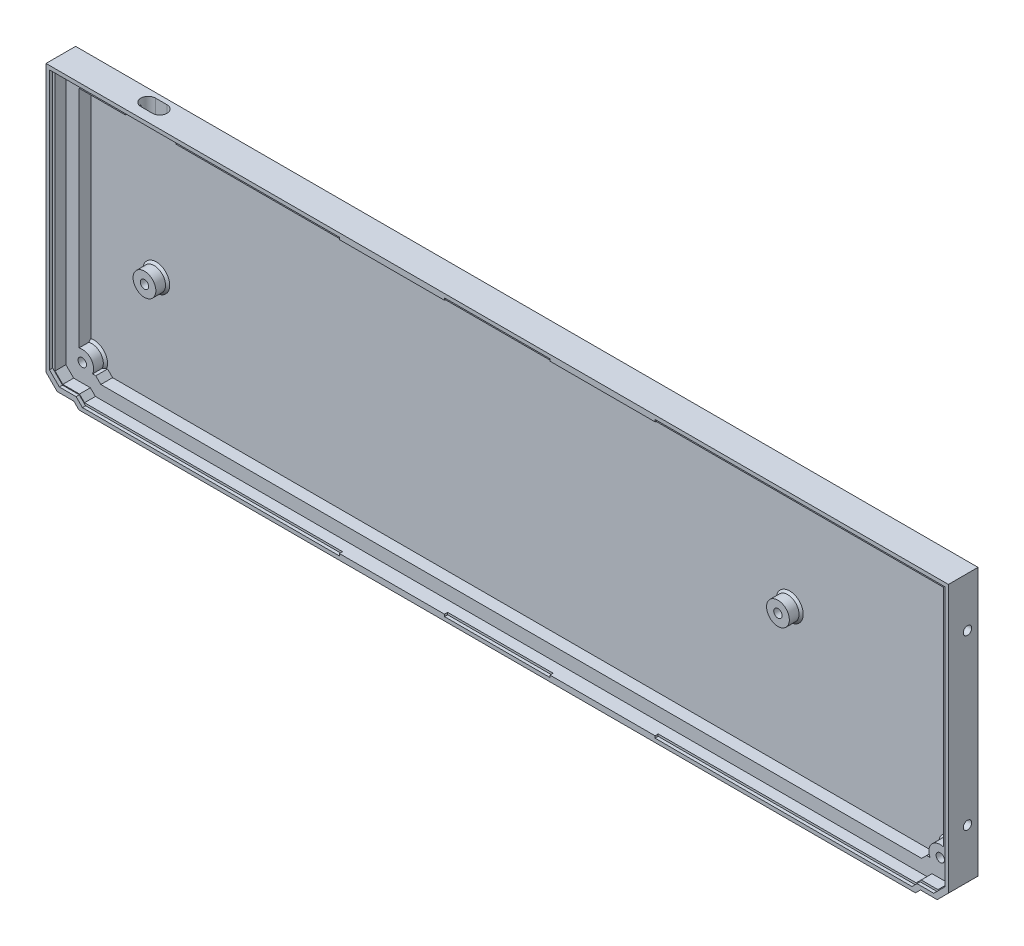
SolidWorks part; units mm, degrees
ref_plane "Přední rovina" through (0, 0, 0) normal (0, 0, 1) x (1, 0, 0)
ref_plane "Horní rovina" through (0, 0, 0) normal (0, 1, 0) x (1, 0, 0)
ref_plane "Pravá rovina" through (0, 0, 0) normal (1, 0, 0) x (0, 0, -1)
sketch "Skica3" plane through (0, 0, 0) normal (0, 0, 1) x (1, 0, 0)
  line L0 (0, 0) -> (415.1053, 0) construction
  line L1 (415.1053, 0) -> (416.6927, -1.5875) construction
  line L2 (416.6927, -1.5875) -> (416.6927, -119.8485) construction
  line L3 (0, 0) -> (-1.5875, -1.5875) construction
  line L4 (-1.5875, -1.5875) -> (-1.5875, -119.8485) construction
  line L5 (-1.5875, -119.8485) -> (0.7934, -122.2292) construction
  line L6 (0.7934, -122.2292) -> (8.7304, -122.2292) construction
  line L7 (8.7304, -122.2292) -> (11.1113, -124.61) construction
  line L8 (11.1113, -124.61) -> (403.9933, -124.61) construction
  line L9 (403.9933, -124.61) -> (406.3744, -122.2294) construction
  line L10 (406.3744, -122.2294) -> (414.3114, -122.2294) construction
  line L11 (416.6927, -119.8485) -> (414.3114, -122.2294) construction
  line L12 (2.4125, -4) -> (412.6927, -4)
  line L13 (412.6927, -4) -> (412.6927, -4)
  line L14 (412.6927, -4) -> (412.6927, -118.1914)
  line L15 (412.6927, -118.1914) -> (412.6547, -118.2294)
  line L16 (404.7177, -118.2294) -> (412.6547, -118.2294)
  line L17 (402.3367, -120.61) -> (404.7177, -118.2294)
  line L18 (12.7681, -120.61) -> (402.3367, -120.61)
  line L19 (10.3872, -118.2292) -> (12.7681, -120.61)
  line L20 (2.4502, -118.2292) -> (10.3872, -118.2292)
  line L21 (2.4125, -118.1915) -> (2.4502, -118.2292)
  line L22 (2.4125, -4) -> (2.4125, -118.1915)
  line L23 (2.4125, -4) -> (2.4125, -4)
  line L24 (-1.5875, -119.8485) -> (415.1053, 0) construction
  line L26 (0, 0) -> (416.6927, -119.8485) construction
  dimension "D1" = 135
  dimension "D2" = 135
  dimension "D3" = 4
  dimension "D4" = 2.245
  dimension "D5" = 2.245
  dimension "D6" = 118.261
  dimension "D7" = 118.261
  dimension "D8" = 3.367
  dimension "D9" = 7.937
  dimension "D10" = 3.367
  dimension "D11" = 392.882
  dimension "D12" = 3.367
  dimension "D13" = 7.937
  dimension "D14" = 3.3674
extrude "Přidat vysunutím1" add sketch "Skica3" along normal blind 5.6
shell "Skořepina1" thickness 1.8 removed face at (207.5525, -95.852, 5.6) outward yes
sketch "Skica7" plane through (0, 0, 5.6) normal (0, 0, 1) x (1, 0, 0)
  line L20 (-6.5875, 5) -> (-6.5875, -121.9196)
  line L21 (-6.5875, -121.9196) -> (-1.2775, -127.2292)
  line L22 (-1.2775, -127.2292) -> (6.6595, -127.2292)
  line L23 (6.6595, -127.2292) -> (9.0403, -129.61)
  line L24 (9.0403, -129.61) -> (406.0641, -129.61)
  line L25 (406.0641, -129.61) -> (408.4452, -127.2294)
  line L26 (408.4452, -127.2294) -> (416.3822, -127.2294)
  line L27 (416.3822, -127.2294) -> (421.6927, -121.9198)
  line L28 (421.6927, -121.9198) -> (421.6927, 5)
  line L29 (421.6927, 5) -> (-6.5875, 5)
  line L30 (-6.5875, 5) -> (-6.5875, -121.9196)
  line L31 (-6.5875, -121.9196) -> (-1.2775, -127.2292)
  line L32 (-1.2775, -127.2292) -> (6.6595, -127.2292)
  line L33 (6.6595, -127.2292) -> (9.0403, -129.61)
  line L34 (9.0403, -129.61) -> (406.0641, -129.61)
  line L35 (406.0641, -129.61) -> (408.4452, -127.2294)
  line L36 (408.4452, -127.2294) -> (416.3822, -127.2294)
  line L37 (416.3822, -127.2294) -> (421.6927, -121.9198)
  line L38 (421.6927, -121.9198) -> (421.6927, 5)
  line L39 (421.6927, 5) -> (-6.5875, 5)
  line L40 (-3.7875, 2.2) -> (-3.7875, -120.7598)
  line L41 (-3.7875, -120.7598) -> (-0.1178, -124.4292)
  line L42 (-0.1178, -124.4292) -> (7.8192, -124.4292)
  line L43 (7.8192, -124.4292) -> (10.2001, -126.81)
  line L44 (10.2001, -126.81) -> (404.9045, -126.81)
  line L45 (404.9045, -126.81) -> (407.2855, -124.4294)
  line L46 (407.2855, -124.4294) -> (415.2225, -124.4294)
  line L47 (415.2225, -124.4294) -> (418.8927, -120.7598)
  line L48 (418.8927, -120.7598) -> (418.8927, 2.2)
  line L49 (418.8927, 2.2) -> (-3.7875, 2.2)
  line L50 (-3.7875, 2.2) -> (-3.7875, -120.7598)
  line L51 (-3.7875, -120.7598) -> (-0.1178, -124.4292)
  line L52 (-0.1178, -124.4292) -> (7.8192, -124.4292)
  line L53 (7.8192, -124.4292) -> (10.2001, -126.81)
  line L54 (10.2001, -126.81) -> (404.9045, -126.81)
  line L55 (404.9045, -126.81) -> (407.2855, -124.4294)
  line L56 (407.2855, -124.4294) -> (415.2225, -124.4294)
  line L57 (415.2225, -124.4294) -> (418.8927, -120.7598)
  line L58 (418.8927, -120.7598) -> (418.8927, 2.2)
  line L59 (418.8927, 2.2) -> (-3.7875, 2.2)
  dimension "D2" = 4.4
  dimension "D1" = 7.2
extrude "Přidat vysunutím3" add sketch "Skica7" along normal blind 5.15 separate body
sketch "Skica8" plane through (0, 0, 5.6) normal (0, 0, -1) x (-1, 0, 0)
  line L0 (-421.6927, 5) -> (6.5875, 5)
  line L1 (6.5875, 5) -> (6.5875, -121.9196)
  line L2 (6.5875, 5) -> (6.5875, -121.9196) construction
  line L3 (6.5875, -121.9196) -> (1.2775, -127.2292)
  line L4 (1.2775, -127.2292) -> (-6.6595, -127.2292)
  line L5 (-6.6595, -127.2292) -> (-9.0403, -129.61)
  line L6 (-9.0403, -129.61) -> (-406.0641, -129.61)
  line L7 (-406.0641, -129.61) -> (-408.4452, -127.2294)
  line L8 (-408.4452, -127.2294) -> (-416.3822, -127.2294)
  line L9 (-416.3822, -127.2294) -> (-421.6927, -121.9198)
  line L10 (-421.6927, -121.9198) -> (-421.6927, 5)
  line L11 (-0.6125, -2.2) -> (-0.6125, -118.9371)
  line L12 (-414.4927, -2.2) -> (-0.6125, -2.2) construction
  line L13 (-0.6125, -2.2) -> (-0.6125, -118.9371) construction
  line L14 (-0.6125, -118.9371) -> (-1.7047, -120.0292)
  line L15 (-1.7047, -120.0292) -> (-9.6417, -120.0292)
  line L16 (-9.6417, -120.0292) -> (-12.0226, -122.41)
  line L17 (-12.0226, -122.41) -> (-403.0822, -122.41)
  line L18 (-403.0822, -122.41) -> (-405.4632, -120.0294)
  line L19 (-405.4632, -120.0294) -> (-413.4002, -120.0294) construction
  line L20 (-405.4632, -120.0294) -> (-413.4002, -120.0294)
  line L21 (-413.4002, -120.0294) -> (-414.4927, -118.9371) construction
  line L22 (-413.4002, -120.0294) -> (-414.4927, -118.9371)
  line L23 (-414.4927, -118.9371) -> (-414.4927, -2.2)
  line L24 (-414.4927, -2.2) -> (-0.6125, -2.2)
extrude "Přidat vysunutím4" add sketch "Skica8" along normal up to surface (7.4 mm away) up to face at (207.5525, -96.7211, -1.8)
sketch "Skica11" plane through (0, 0, 10.75) normal (0, 0, 1) x (1, 0, 0)
  line L0 (207.5526, 3.195) -> (207.5526, 5) construction
  line L1 (421.6927, 5) -> (-6.5875, 5) construction
  line L2 (207.5522, -127.805) -> (207.5522, -129.61) construction
  line L3 (9.0403, -129.61) -> (406.0641, -129.61) construction
  line L4 (-4.9474, -58.4598) -> (-6.5875, -58.4598) construction
  line L5 (-6.5875, 5) -> (-6.5875, -121.9196) construction
  line L6 (420.0526, -58.4599) -> (421.6927, -58.4599) construction
  line L7 (421.6927, -121.9198) -> (421.6927, 5) construction
  line L8 (404.9045, -126.81) -> (407.2855, -124.4294) construction
  line L9 (415.2225, -124.4294) -> (418.8927, -120.7598) construction
  line L10 (7.8192, -124.4292) -> (10.2001, -126.81) construction
  line L11 (-3.7875, -120.7598) -> (-0.1178, -124.4292) construction
  line L13 (407.2855, -124.4294) -> (415.2225, -124.4294) construction
  line L14 (-0.1178, -124.4292) -> (7.8192, -124.4292) construction
  line L30 (420.0526, 3.195) -> (-4.9474, 3.195)
  line L31 (-4.9474, 3.195) -> (-4.9474, -120.1146)
  line L32 (-4.9474, -120.1146) -> (-0.24, -124.8217)
  line L33 (-0.24, -124.8217) -> (7.697, -124.8217)
  line L34 (7.697, -124.8217) -> (10.6804, -127.805)
  line L35 (10.6804, -127.805) -> (404.4241, -127.805)
  line L36 (404.4241, -127.805) -> (406.8051, -125.4244)
  line L37 (406.8051, -125.4244) -> (414.7421, -125.4244)
  line L38 (414.7421, -125.4244) -> (420.0526, -120.1148)
  line L39 (420.0526, -120.1148) -> (420.0526, 3.195)
  line L45 (421.6927, 5) -> (-6.5875, 5)
  line L46 (-6.5875, 5) -> (-6.5875, -121.9196)
  line L47 (-6.5875, -121.9196) -> (-1.2775, -127.2292)
  line L48 (-1.2775, -127.2292) -> (6.6595, -127.2292)
  line L49 (6.6595, -127.2292) -> (9.0403, -129.61)
  line L50 (9.0403, -129.61) -> (406.0641, -129.61)
  line L51 (406.0641, -129.61) -> (408.4452, -127.2294)
  line L52 (408.4452, -127.2294) -> (416.3822, -127.2294)
  line L53 (416.3822, -127.2294) -> (421.6927, -121.9198)
  line L54 (421.6927, -121.9198) -> (421.6927, 5)
  line L55 (421.6927, 5) -> (-6.5875, 5)
  line L56 (-6.5875, 5) -> (-6.5875, -121.9196)
  line L57 (-6.5875, -121.9196) -> (-1.2775, -127.2292)
  line L58 (-1.2775, -127.2292) -> (6.6595, -127.2292)
  line L59 (6.6595, -127.2292) -> (9.0403, -129.61)
  line L60 (9.0403, -129.61) -> (406.0641, -129.61)
  line L61 (406.0641, -129.61) -> (408.4452, -127.2294)
  line L62 (408.4452, -127.2294) -> (416.3822, -127.2294)
  line L63 (416.3822, -127.2294) -> (421.6927, -121.9198)
  line L64 (421.6927, -121.9198) -> (421.6927, 5)
  point P0 (207.5523, -63.11)
  point P2 (207.5523, -63.11)
  point P25 (0, 0)
  point P27 (0, 0)
  dimension "D1" = 131
  dimension "D2" = 425
  dimension "D3" = 0
extrude "Přidat vysunutím5" add sketch "Skica11" along normal blind 1.5
sketch "Skica14" plane through (0, 0, 10.75) normal (0, 0, 1) x (1, 0, 0)
  line L0 (418.8927, 2.2) -> (-3.7875, 2.2) construction
  line L1 (182.5326, 2.2) -> (132.6326, 2.2)
  line L2 (182.5326, 2.2) -> (182.5326, 3.195)
  line L3 (182.5326, 3.195) -> (132.6326, 3.195)
  line L4 (132.6326, 2.2) -> (132.6326, 3.195)
  line L5 (420.0526, 3.195) -> (-4.9474, 3.195) construction
  line L6 (418.8927, 2.2) -> (-3.7875, 2.2) construction
  line L7 (232.5726, 2.2) -> (282.4726, 2.2)
  line L8 (232.5726, 2.2) -> (232.5726, 3.195)
  line L9 (232.5726, 3.195) -> (282.4726, 3.195)
  line L10 (282.4726, 2.2) -> (282.4726, 3.195)
  line L11 (207.5526, 3.195) -> (207.5522, -127.805) construction
  line L12 (10.6804, -127.805) -> (404.4241, -127.805) construction
  line L13 (10.2001, -126.81) -> (404.9045, -126.81) construction
  line L14 (232.5722, -126.81) -> (282.4722, -126.81)
  line L15 (232.5722, -126.81) -> (232.5722, -127.805)
  line L16 (232.5722, -127.805) -> (282.4722, -127.805)
  line L17 (282.4722, -126.81) -> (282.4722, -127.805)
  line L18 (10.6804, -127.805) -> (404.4241, -127.805) construction
  line L20 (182.5322, -126.81) -> (132.6322, -126.81)
  line L21 (182.5322, -126.81) -> (182.5322, -127.805)
  line L22 (182.5322, -127.805) -> (132.6322, -127.805)
  line L23 (132.6322, -126.81) -> (132.6322, -127.805)
  dimension "D1" = 49.9
  dimension "D2" = 49.9
  dimension "D3" = 25.02
  dimension "D4" = 25.02
  dimension "D5" = 49.9
  dimension "D6" = 49.9
  dimension "D7" = 25.02
  dimension "D8" = 25.02
extrude "Přidat vysunutím6" add sketch "Skica14" along normal up to surface (1.5 mm away) up to face at (207.5524, -100.1977, 12.25)
sketch "Skica15" plane through (0, 0, 0) normal (0, 0, 1) x (1, 0, 0)
  line L1 (34.9015, 4.5) -> (37.9015, 4.5)
  line L2 (34.9015, 4.5) -> (34.9015, -4.5)
  line L3 (34.9015, -4.5) -> (37.9015, -4.5)
  line L4 (37.9015, 4.5) -> (37.9015, -4.5)
  line L5 (34.9015, 4.5) -> (37.9015, -4.5) construction
  line L6 (34.9015, -4.5) -> (37.9015, 4.5) construction
  line L20 (-1.5875, 0) -> (-1.5875, -119.8485)
  line L21 (-1.5875, -119.8485) -> (0.7934, -122.2292)
  line L22 (0.7934, -122.2292) -> (8.7304, -122.2292)
  line L23 (8.7304, -122.2292) -> (11.1113, -124.61)
  line L24 (11.1113, -124.61) -> (403.9933, -124.61)
  line L25 (403.9933, -124.61) -> (406.3744, -122.2294)
  line L26 (406.3744, -122.2294) -> (414.3114, -122.2294)
  line L27 (414.3114, -122.2294) -> (416.6927, -119.8485)
  line L28 (416.6927, -119.8485) -> (416.6927, 0)
  line L29 (416.6927, 0) -> (-1.5875, 0)
  line L30 (-1.5875, 0) -> (-1.5875, -119.8485) construction
  line L31 (-1.5875, -119.8485) -> (0.7934, -122.2292) construction
  line L32 (0.7934, -122.2292) -> (8.7304, -122.2292) construction
  line L33 (8.7304, -122.2292) -> (11.1113, -124.61) construction
  line L34 (11.1113, -124.61) -> (403.9933, -124.61) construction
  line L35 (403.9933, -124.61) -> (406.3744, -122.2294) construction
  line L36 (406.3744, -122.2294) -> (414.3114, -122.2294) construction
  line L37 (414.3114, -122.2294) -> (416.6927, -119.8485) construction
  line L38 (416.6927, -119.8485) -> (416.6927, 0) construction
  line L39 (416.6927, 0) -> (-1.5875, 0) construction
  circle A0 centre (3.9685, -115.9542) radius 5.4
  circle A1 centre (33.4915, -69.051) radius 5.4
  circle A2 centre (411.1977, -115.8794) radius 5.4
  circle A3 centre (334.1477, -53.972) radius 5.4
  point P2 (-1.4315, -115.9542)
  point P3 (3.9685, -121.3542)
  point P4 (28.0915, -69.051)
  point P8 (33.4915, -74.451)
  point P12 (411.1977, -121.2794)
  point P13 (416.5977, -115.8794)
  point P17 (334.1477, -48.572)
  point P19 (339.5477, -53.972)
  point P21 (36.4015, 0)
  point P23 (36.4015, 0)
  dimension "D2" = 0.156
  dimension "D4" = 10.8
  dimension "D7" = 10.8
  dimension "D10" = 10.8
  dimension "D13" = 10.8
  dimension "D3" = 0.875
  dimension "D5" = 29.679
  dimension "D6" = 50.159
  dimension "D8" = 0.095
  dimension "D9" = 0.95
  dimension "D11" = 77.145
  dimension "D12" = 48.572
  dimension "D14" = 37.989
  dimension "D15" = 9
  dimension "D16" = 3
  dimension "D1" = 4
extrude "Přidat vysunutím7" add sketch "Skica15" along normal blind 5.6
sketch "Skica16" plane through (0, 0, 5.6) normal (0, 0, 1) x (1, 0, 0)
  circle A0 centre (3.9685, -115.9542) radius 2
  circle A1 centre (33.4915, -69.051) radius 2
  circle A2 centre (334.1477, -53.972) radius 2
  circle A3 centre (411.1977, -115.8794) radius 2
  dimension "D1" = 4
  dimension "D2" = 4
  dimension "D3" = 4
  dimension "D4" = 4
extrude "Odebrat vysunutím1" cut sketch "Skica16" against normal blind 5.75
chamfer "Zkosení1" distance 1 angle 45 4 edges at (407.0694, -112.3984, 0) (8.0492, -112.4175, 0) (38.8915, -69.051, 0) (339.5477, -53.972, 0)
sketch "Skica17" plane through (0, 0, 5.6) normal (0, 0, 1) x (1, 0, 0)
  line L0 (34.9015, -4.5) -> (37.9015, -4.5) construction
  line L1 (24.4015, -11.2) -> (48.4015, -11.2)
  line L2 (24.4015, -11.2) -> (24.4015, 2.2)
  line L3 (24.4015, 2.2) -> (48.4015, 2.2)
  line L4 (48.4015, -11.2) -> (48.4015, 2.2)
  line L5 (24.4015, -11.2) -> (48.4015, 2.2) construction
  line L6 (24.4015, 2.2) -> (48.4015, -11.2) construction
  line L7 (418.8927, 2.2) -> (-3.7875, 2.2) construction
  point P0 (36.4015, -4.5)
  dimension "D1" = 24
extrude "Odebrat vysunutím2" cut sketch "Skica17" against normal blind 1.6
sketch "Skica18" plane through (0, -4.5, 0) normal (0, -1, 0) x (1, 0, 0)
  line L0 (33.6515, 4) -> (39.1515, 4) construction
  line L1 (37.9015, 4) -> (34.9015, 4) construction
  line L2 (37.9015, 4) -> (48.4015, 4) construction
  line L3 (33.6515, 7.5) -> (39.1515, 7.5)
  line L4 (33.6515, 0.5) -> (39.1515, 0.5)
  arc A0 (33.6515, 7.5) -> (33.6515, 0.5) centre (33.6515, 4) ccw
  arc A1 (39.1515, 0.5) -> (39.1515, 7.5) centre (39.1515, 4) ccw
  point P6 (36.4015, 4)
  point P11 (30.1515, 4)
  point P12 (42.6515, 4)
  dimension "D1" = 12.5
  dimension "D2" = 7
extrude "Odebrat vysunutím3" cut sketch "Skica18" against normal up to surface (9.5 mm away) up to face at (207.5526, 5, 5.225)
sketch "Skica23" plane through (-6.5875, 0, 0) normal (-1, 0, 0) x (0, 0, 1)
  line L2 (-1.8, 5) -> (-1.8, -121.9196) construction
  line L4 (-1.8, -58.4598) -> (12.25, -58.4598) construction
  line L5 (12.25, 5) -> (12.25, -121.9196) construction
  circle A0 centre (3.2, -18.4598) radius 2
  circle A1 centre (3.2, -98.4598) radius 2
  point P8 (-1.8, -58.4598)
  dimension "D2" = 4
  dimension "D3" = 4
  dimension "D1" = 40
  dimension "D4" = 5
extrude "Odebrat vysunutím4" cut sketch "Skica23" against normal blind 5.7
sketch "Skica24" plane through (421.6927, 0, 0) normal (1, 0, 0) x (0, 0, -1)
  line L0 (1.8, -58.4599) -> (-12.25, -58.4599) construction
  line L1 (1.8, -121.9198) -> (1.8, 5) construction
  line L2 (-12.25, -121.9198) -> (-12.25, 5) construction
  circle A0 centre (-3.2, -18.4599) radius 2
  circle A1 centre (-3.2, -98.4599) radius 2
  dimension "D1" = 4
  dimension "D2" = 4
  dimension "D3" = 40
  dimension "D4" = 5
extrude "Odebrat vysunutím5" cut sketch "Skica24" against normal blind 5.7
